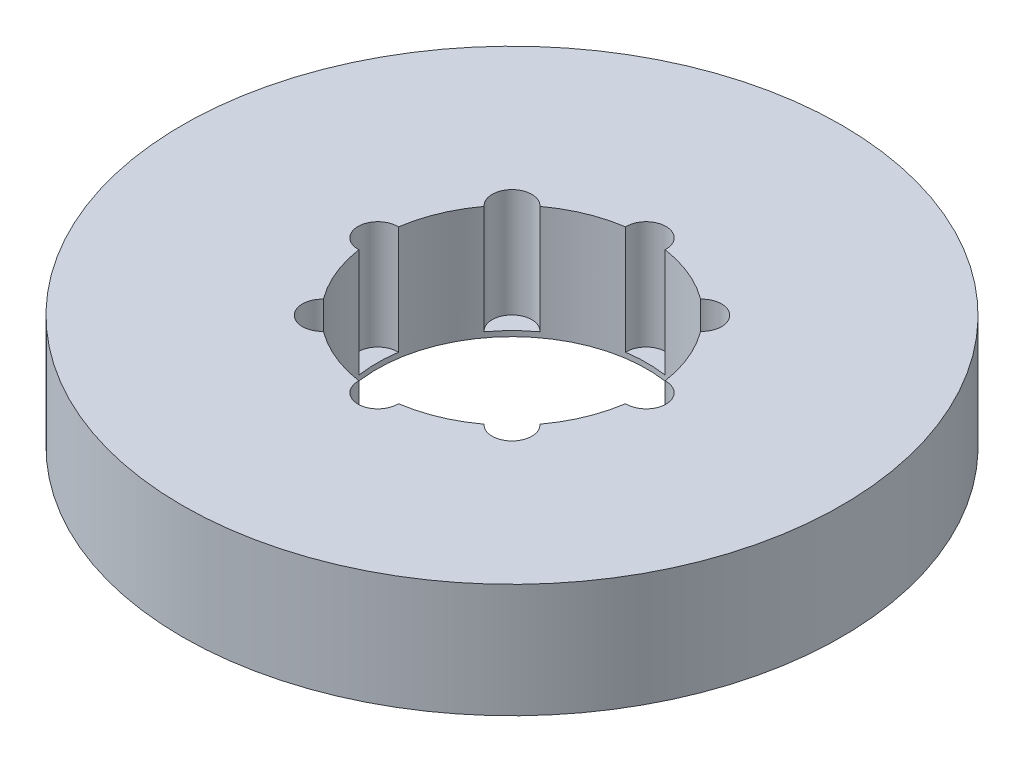
SolidWorks part; units mm, degrees
ref_plane "Front Plane" through (0, 0, 0) normal (0, 0, 1) x (1, 0, 0)
ref_plane "Top Plane" through (0, 0, 0) normal (0, 1, 0) x (1, 0, 0)
ref_plane "Right Plane" through (0, 0, 0) normal (1, 0, 0) x (0, 0, -1)
sketch "Sketch1" plane through (0, 0, 0) normal (0, 1, 0) x (1, 0, 0)
  circle A0 centre (0, 0) radius 55
  dimension "FLANGE_OD" = 110
extrude "Boss-Extrude1" add sketch "Sketch1" along normal blind 19
sketch "Sketch2" plane through (0, 0, 0) normal (0, 1, 0) x (1, 0, 0)
  circle A0 centre (0, 0) radius 22.5
  dimension "BORE_D" = 45
extrude "Cut-Extrude1" cut sketch "Sketch2" along normal through all
sketch "Sketch3" plane through (0, 19, 0) normal (0, 1, 0) x (1, 0, 0)
  circle A0 centre (0, 0) radius 22.3926 construction
  circle A1 centre (-22.3926, 0) radius 3.3011
  dimension "BOLT_D" = 6.6022
  dimension "BOLT_PCD" = 44.7852
extrude "Cut-Extrude2" cut sketch "Sketch3" against normal blind 18.1217
pattern_circular "CirPattern1" count 8 over 360 about axis through (0, 0, 0) along (0, 1, 0) of "Cut-Extrude2"
